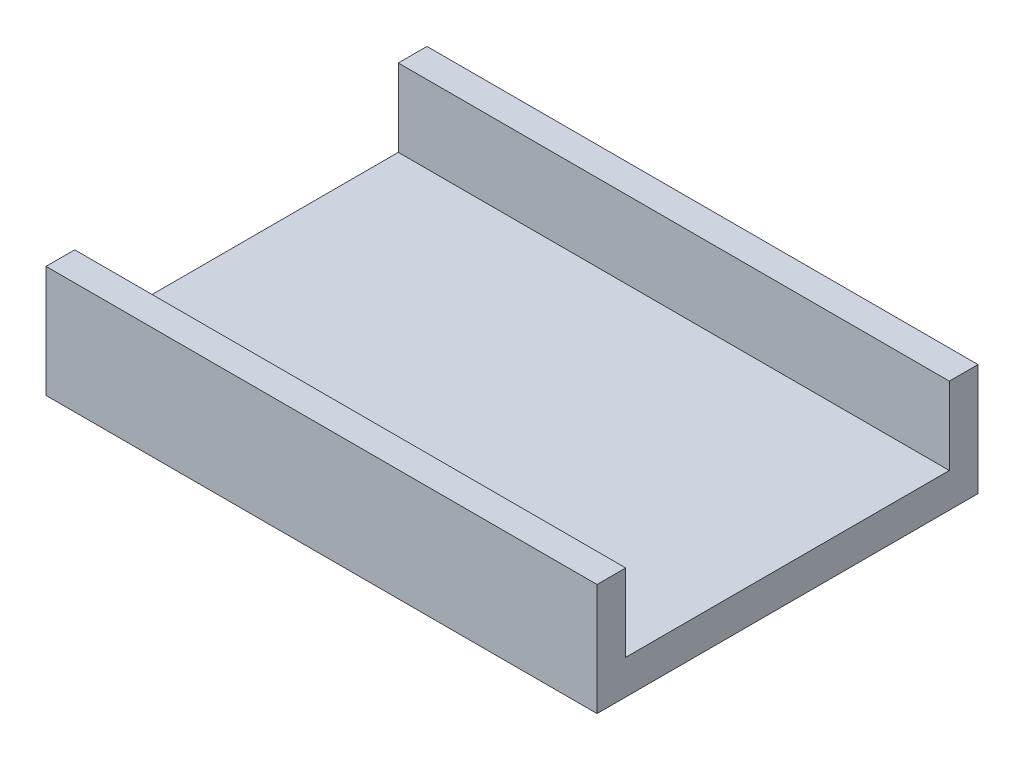
SolidWorks part; units mm, degrees
material "ABS"
ref_plane "Front Plane" through (0, 0, 0) normal (0, 0, 1) x (1, 0, 0)
ref_plane "Top Plane" through (0, 0, 0) normal (0, 1, 0) x (1, 0, 0)
ref_plane "Right Plane" through (0, 0, 0) normal (1, 0, 0) x (0, 0, -1)
sketch "Sketch1" plane through (0, 0, 0) normal (0, 1, 0) x (1, 0, 0)
  line L1 (48.8, 33.2187) -> (-48.8, 33.2187)
  line L2 (48.8, 33.2187) -> (48.8, -33.2187)
  line L3 (48.8, -33.2187) -> (-48.8, -33.2187)
  line L4 (-48.8, 33.2187) -> (-48.8, -33.2187)
  line L5 (48.8, 33.2187) -> (-48.8, -33.2187) construction
  line L6 (48.8, -33.2187) -> (-48.8, 33.2187) construction
  point P0 (0, 0)
  dimension "D1" = 97.6
  dimension "D2" = 66.4375
extrude "Boss-Extrude1" add sketch "Sketch1" along normal blind 6
sketch "Sketch3" plane through (0, 6, 0) normal (0, 1, 0) x (1, 0, 0)
  line L0 (48.8, -33.2187) -> (48.8, 33.2187) construction
  line L1 (30.8, 27) -> (-24.2, 27)
  line L2 (30.8, 27) -> (30.8, -27)
  line L3 (30.8, -27) -> (-24.2, -27)
  line L4 (-24.2, 27) -> (-24.2, -27)
  line L5 (30.8, 27) -> (-24.2, -27) construction
  line L6 (30.8, -27) -> (-24.2, 27) construction
  point P0 (3.3, 0)
  dimension "D1" = 54
  dimension "D2" = 55
  dimension "D3" = 0
  dimension "D4" = 18
sketch "Sketch4" plane through (0, 6, 0) normal (0, 1, 0) x (1, 0, 0)
  line L0 (30.8, -27) -> (30.8, -33.2187)
  line L1 (-48.8, -33.2187) -> (48.8, -33.2187) construction
  line L2 (30.8, -33.2187) -> (30.8, 33.2187)
  line L3 (48.8, 33.2187) -> (-48.8, 33.2187) construction
  line L4 (30.8, 33.2187) -> (30.8, 27)
  line L5 (30.8, 27) -> (48.8, 27)
  line L6 (48.8, -33.2187) -> (48.8, 33.2187) construction
  line L7 (48.8, 27) -> (-48.8, 27)
  line L8 (-48.8, 33.2187) -> (-48.8, -33.2187) construction
  line L9 (-48.8, 27) -> (-24.2, 27)
  line L10 (-24.2, 27) -> (-24.2, 33.2187)
  line L11 (-24.2, 33.2187) -> (-24.2, -33.2187)
  line L13 (-24.2, -33.2187) -> (-48.8, -33.2187)
  line L14 (-24.2, -33.2187) -> (-24.2, 33.2187)
  line L15 (-24.2, 33.2187) -> (-48.8, 33.2187)
  line L16 (-48.8, -33.2187) -> (-48.8, 33.2187)
  line L17 (-48.8, 33.2187) -> (48.8, 33.2187)
  line L18 (-48.8, 33.2187) -> (-48.8, 27)
  line L19 (-48.8, 27) -> (48.8, 27)
  line L20 (48.8, 33.2187) -> (48.8, 27)
  line L21 (48.8, 33.2187) -> (30.8, 33.2187)
  line L22 (48.8, 33.2187) -> (48.8, -33.2187)
  line L23 (48.8, -33.2187) -> (30.8, -33.2187)
  line L24 (30.8, 33.2187) -> (30.8, -33.2187)
  line L25 (48.8, -33.2187) -> (-48.8, -33.2187)
  line L26 (48.8, -33.2187) -> (48.8, -27)
  line L27 (48.8, -27) -> (-48.8, -27)
  line L28 (-48.8, -33.2187) -> (-48.8, -27)
  line M1 (-48.8, 33.2187) -> (-48.8, -33.2187)
  line M2 (-48.8, -33.2187) -> (48.8, -33.2187)
  line M3 (48.8, -33.2187) -> (48.8, 33.2187)
  line M4 (48.8, 33.2187) -> (-48.8, 33.2187)
extrude "Boss-Extrude2" add sketch "Sketch4" along normal blind 13.5 contours L27 L11 L7 M1 | L14 L27 L16 M2 | L0 L27 L14 M2 | L27 L0 M3 M2 | L27 L22 L5 L2 | L2 L5 M3 M4 | L7 L10 M4 M1 | L10 L7 L2 M4 region at (39.8, 6, 30.1094) region at (39.8, 6, 0) region at (3.3, 6, 30.1094) region at (3.3, 6, -30.1094) region at (39.8, 6, -30.1094) region at (-36.5, 6, 0) region at (-36.5, 6, 30.1094) region at (-36.5, 6, -30.1094)
sketch "Sketch5" plane through (0, 19.5, 0) normal (0, 1, 0) x (1, 0, 0)
  line L0 (-46.8936, -20) -> (-12.1997, -20)
  line L1 (-46.8936, -20) -> (-46.8936, 10)
  line L2 (-12.1997, -20) -> (-12.1997, 10)
  line L3 (-46.8936, 10) -> (-12.1997, 10)
  line L4 (-46.8936, -20) -> (-12.1997, 10) construction
  line L5 (-12.1997, -20) -> (-46.8936, 10) construction
  point P1 (-29.5467, -5)
  dimension "D1" = 30
  dimension "D2" = 5
extrude "Cut-Extrude1" [suppressed] cut sketch "Sketch5" against normal blind 13.5
sketch "Sketch6" plane through (0, 19.5, 0) normal (0, 1, 0) x (1, 0, 0)
  line L0 (48.8, -33.2187) -> (48.8, 33.2187) construction
  line L1 (48.8, 28.2187) -> (-48.8, 28.2187)
  line L2 (48.8, 28.2187) -> (48.8, -28.2187)
  line L3 (48.8, -28.2187) -> (-48.8, -28.2187)
  line L4 (-48.8, 28.2187) -> (-48.8, -28.2187)
  line L5 (-48.8, 33.2187) -> (-48.8, -33.2187) construction
  line L6 (48.8, 33.2187) -> (-48.8, 33.2187) construction
  line L7 (-48.8, -33.2187) -> (48.8, -33.2187) construction
  dimension "D1" = 5
  dimension "D2" = 5
extrude "Cut-Extrude2" cut sketch "Sketch6" against normal blind 13.5
sketch "Sketch7" plane through (48.8, 0, 0) normal (1, 0, 0) x (0, 0, -1)
  line L1 (33.2187, 0) -> (-33.2187, 0)
  line L2 (33.2187, 0) -> (33.2187, 19.5)
  line L3 (33.2187, 19.5) -> (-33.2187, 19.5)
  line L4 (-33.2187, 0) -> (-33.2187, 19.5)
extrude "Cut-Extrude3" cut sketch "Sketch7" against normal blind 0.75
sketch "Sketch8" plane through (-48.8, 0, 0) normal (-1, 0, 0) x (0, 0, 1)
  line L1 (-33.2187, 0) -> (33.2187, 0)
  line L2 (-33.2187, 0) -> (-33.2187, 19.5)
  line L3 (-33.2187, 19.5) -> (33.2187, 19.5)
  line L4 (33.2187, 0) -> (33.2187, 19.5)
extrude "Cut-Extrude4" cut sketch "Sketch8" against normal blind 0.75
